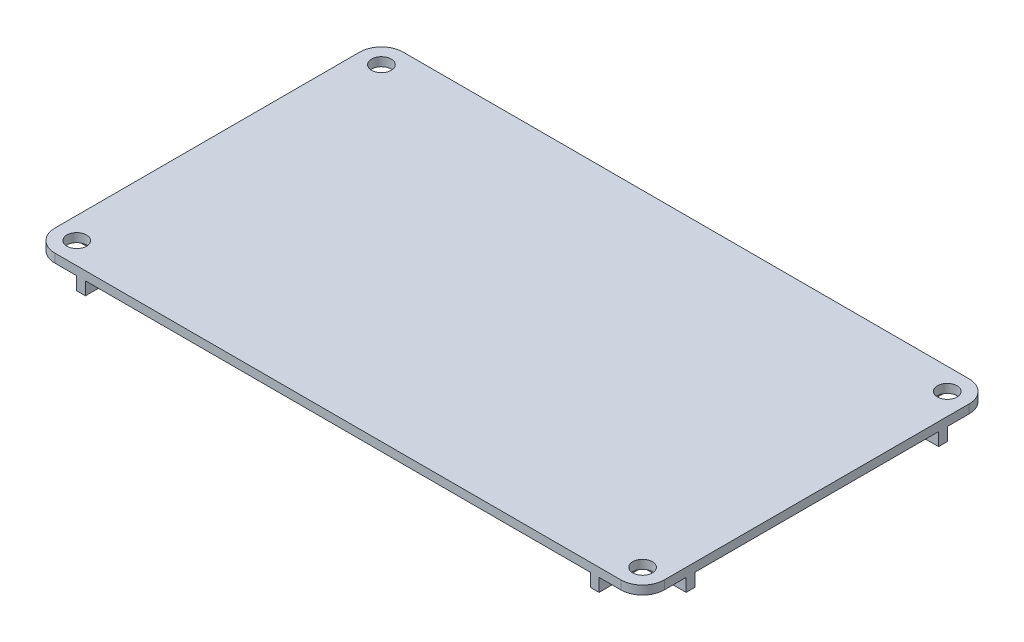
SolidWorks part; units mm, degrees
ref_plane "Front Plane" through (0, 0, 0) normal (0, 0, 1) x (1, 0, 0)
ref_plane "Top Plane" through (0, 0, 0) normal (0, 1, 0) x (1, 0, 0)
ref_plane "Right Plane" through (0, 0, 0) normal (1, 0, 0) x (0, 0, -1)
sketch "Sketch1" plane through (0, 0, 0) normal (0, 1, 0) x (1, 0, 0)
  line L0 (70, 30) -> (60, 30)
  line L1 (-70, 40) -> (70, 40)
  line L2 (-70, 40) -> (-70, -40)
  line L3 (-70, -40) -> (70, -40)
  line L4 (70, 40) -> (70, -40)
  line L5 (-70, 40) -> (70, -40) construction
  line L6 (-70, -40) -> (70, 40) construction
  line L7 (60, 30) -> (60, 40)
  line L8 (0, 0) -> (26.6657, 0) construction
  line L9 (0, 0) -> (0, 20) construction
  line L10 (58, 40) -> (58, 28)
  line L11 (58, 28) -> (70, 28)
  line L12 (-60, 40) -> (-70, 30) construction
  line L13 (-60, 30) -> (-70, 40) construction
  line L14 (-58, 28) -> (-70, 28)
  line L15 (-58, 40) -> (-58, 28)
  line L16 (60, 30) -> (70, 40) construction
  line L17 (60, 40) -> (70, 30) construction
  line L18 (-60, 30) -> (-60, 40)
  line L19 (-70, 30) -> (-60, 30)
  line L20 (60, -40) -> (70, -30) construction
  line L21 (60, -30) -> (70, -40) construction
  line L22 (-60, -30) -> (-70, -40) construction
  line L23 (-60, -40) -> (-70, -30) construction
  line L24 (-70, -30) -> (-60, -30)
  line L25 (-60, -30) -> (-60, -40)
  line L26 (-58, -40) -> (-58, -28)
  line L27 (-58, -28) -> (-70, -28)
  line L28 (58, -28) -> (70, -28)
  line L29 (58, -40) -> (58, -28)
  line L30 (60, -30) -> (60, -40)
  line L31 (70, -30) -> (60, -30)
  circle A0 centre (65, 35) radius 2.25
  circle A1 centre (-65, 35) radius 2.25
  circle A2 centre (-65, -35) radius 2.25
  circle A3 centre (65, -35) radius 2.25
  point P0 (0, 0)
  dimension "D4" = 4.5
  dimension "D1" = 80
  dimension "D2" = 140
  dimension "D3" = 10
  dimension "D5" = 2
extrude "Boss-Extrude4" add sketch "Sketch1" along normal blind 2 contours L3 L29 L28 L4 L11 L10 L1 L15 L14 L2 L27 L26 | L19 L2 L14 L15 L1 L18 | L2 L19 L18 L1 A1 | L7 L0 L4 L1 A0 | L10 L11 L4 L0 L7 L1 | L4 L31 L30 L3 A3 | L31 L4 L28 L29 L3 L30 | L26 L27 L2 L24 L25 L3 | L25 L24 L2 L3 A2 region at (69.8303, 0, -29) region at (65, 0, -30.1414) region at (0, 0, 0) region at (69.8303, 0, 29) region at (69.8586, 0, 35) region at (-58.1697, 0, -34) region at (-60.1414, 0, -35) region at (-59, 0, 39.8303) region at (-65, 0, 39.8586)
extrude "Boss-Extrude5" add sketch "Sketch1<5>" against normal blind 3 contours L26 L27 L2 L24 L25 L3 | L31 L4 L28 L29 L3 L30 | L10 L11 L4 L0 L7 L1 | L19 L2 L14 L15 L1 L18 region at (69.8303, 0, -29) region at (69.8303, 0, 29) region at (-58.1697, 0, -34) region at (-59, 0, 39.8303)
sketch "Sketch1<5>" plane through (0, 0, 0) normal (0, 1, 0) x (1, 0, 0) same geometry as "Sketch1"
fillet "Fillet1" radius 5 4 edges at (70, 1, -40) (-70, 1, -40) (-70, 1, 40) (70, 1, 40)
